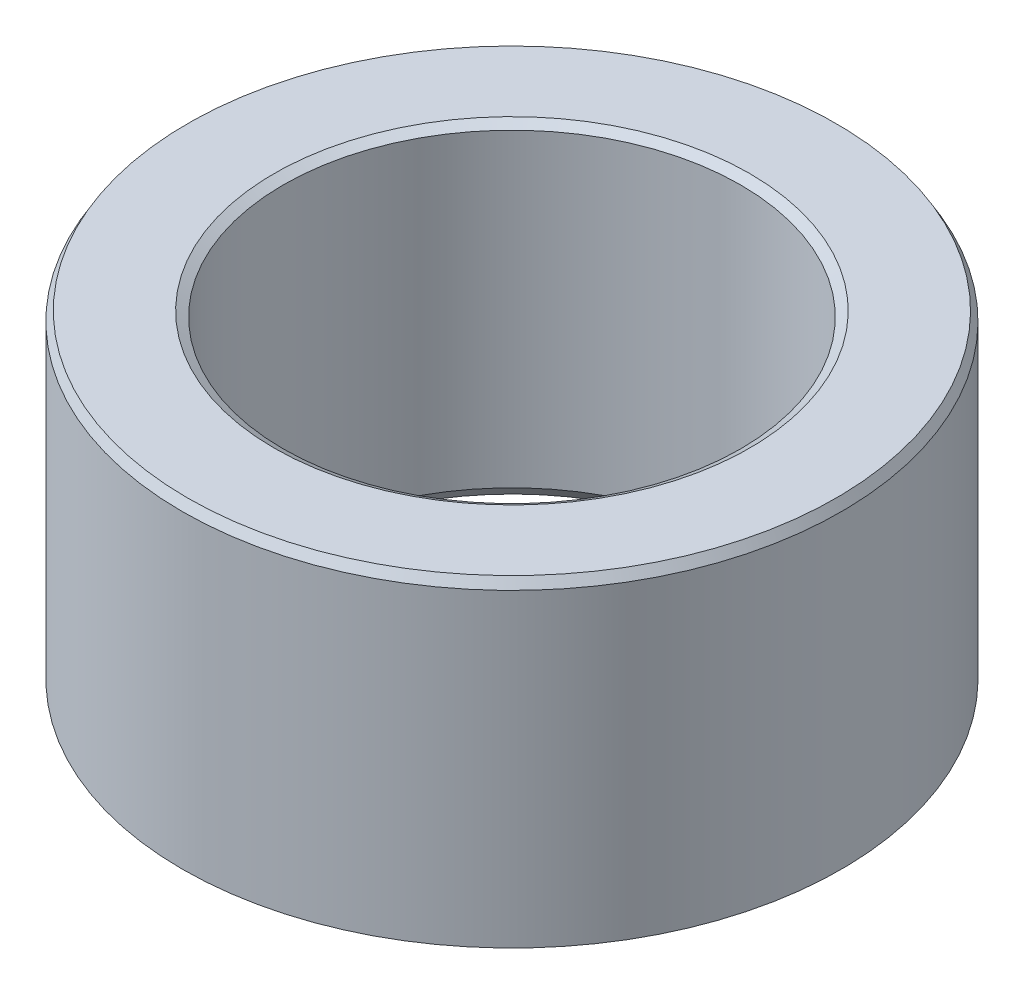
SolidWorks part; units mm, degrees
ref_plane "Front Plane" through (0, 0, 0) normal (0, 0, 1) x (1, 0, 0)
ref_plane "Top Plane" through (0, 0, 0) normal (0, 1, 0) x (1, 0, 0)
ref_plane "Right Plane" through (0, 0, 0) normal (1, 0, 0) x (0, 0, -1)
sketch "Sketch1" plane through (0, 0, 0) normal (0, 1, 0) x (1, 0, 0)
  circle A0 centre (0, 0) radius 12.5
  dimension "SLEEVE_OD" = 25
extrude "Boss-Extrude1" add sketch "Sketch1" along normal blind 12.2934
sketch "Sketch2" plane through (0, 0, 0) normal (0, 1, 0) x (1, 0, 0)
  circle A0 centre (0, 0) radius 8.6734
  dimension "BORE_D" = 17.3469
extrude "Cut-Extrude1" cut sketch "Sketch2" along normal through all
chamfer "Chamfer1" distance 0.3463 angle 30 4 edges at (0, 12.2934, 8.6734) (0, 0, 8.6734) (0, 0, 12.5) (0, 12.2934, 12.5) first distance on face at (0, 12.2934, 8.6734) first distance on face at (0, 0, 8.6734) first distance on face at (0, 12.2934, 12.5)
